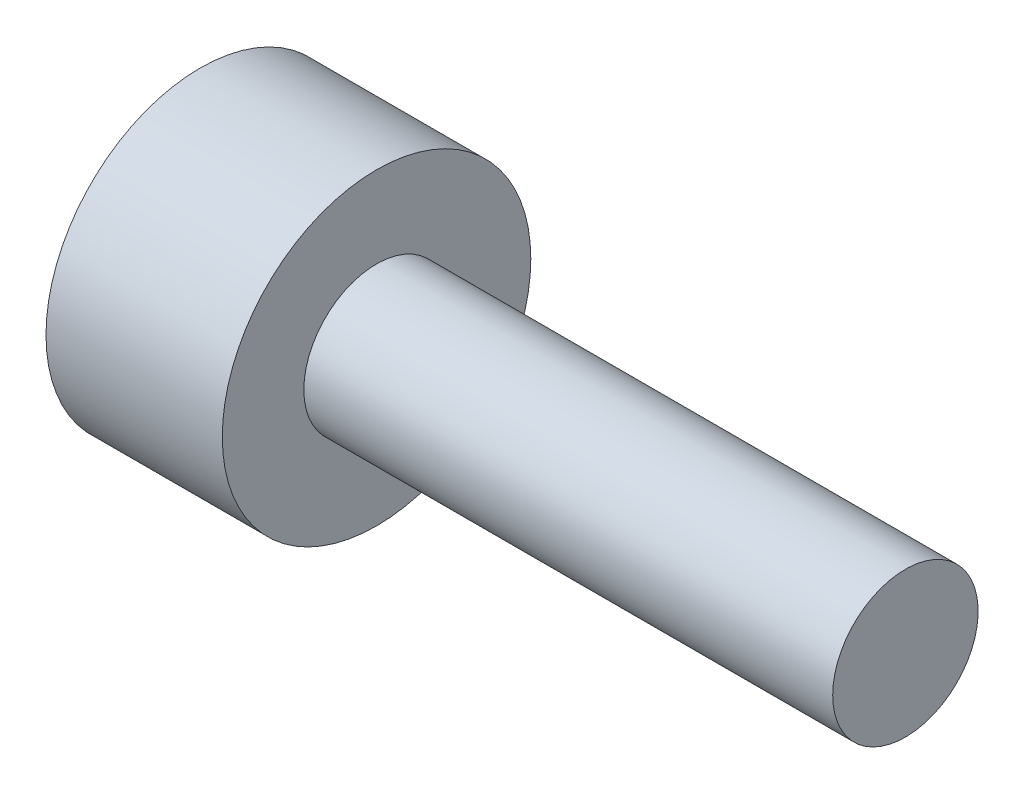
SolidWorks part; units mm, degrees
ref_plane "Front Plane" through (0, 0, 0) normal (0, 0, 1) x (1, 0, 0)
ref_plane "Top Plane" through (0, 0, 0) normal (0, 1, 0) x (1, 0, 0)
ref_plane "Right Plane" through (0, 0, 0) normal (1, 0, 0) x (0, 0, -1)
sketch "Screw Sketch" plane through (0, 0, 0) normal (0, 0, 1) x (1, 0, 0)
  line L0 (-1000, 0) -> (1000, 0) construction
  line L1 (-4, 0) -> (-4, 3.5)
  line L2 (-4, 3.5) -> (0, 3.5)
  line L3 (0, 3.5) -> (0, 1.65)
  line L4 (0, 1.65) -> (12, 1.65)
  line L5 (12, 1.65) -> (12, 0)
  line L6 (12, 0) -> (-4, 0)
revolve "Screw" add sketch "Screw Sketch" angle 360 about L0
ref_axis "Engine Axis" through (12.8, 0, 0) along (-1, 0, 0)
ref_plane "Head Top" through (-4, 0, 0) normal (1, 0, 0) x (0, 0, -1)
sketch "Socket Sketch" plane through (-4, 0, 0) normal (1, 0, 0) x (0, 0, -1)
  line L0 (1.7321, 0) -> (0.866, 1.5)
  line L1 (0.866, 1.5) -> (-0.866, 1.5)
  line L2 (-0.866, 1.5) -> (-1.7321, 0)
  line L3 (-1.7321, 0) -> (-0.866, -1.5)
  line L4 (-0.866, -1.5) -> (0.866, -1.5)
  line L5 (0.866, -1.5) -> (1.7321, 0)
extrude "Socket" cut sketch "Socket Sketch" along normal blind 2
